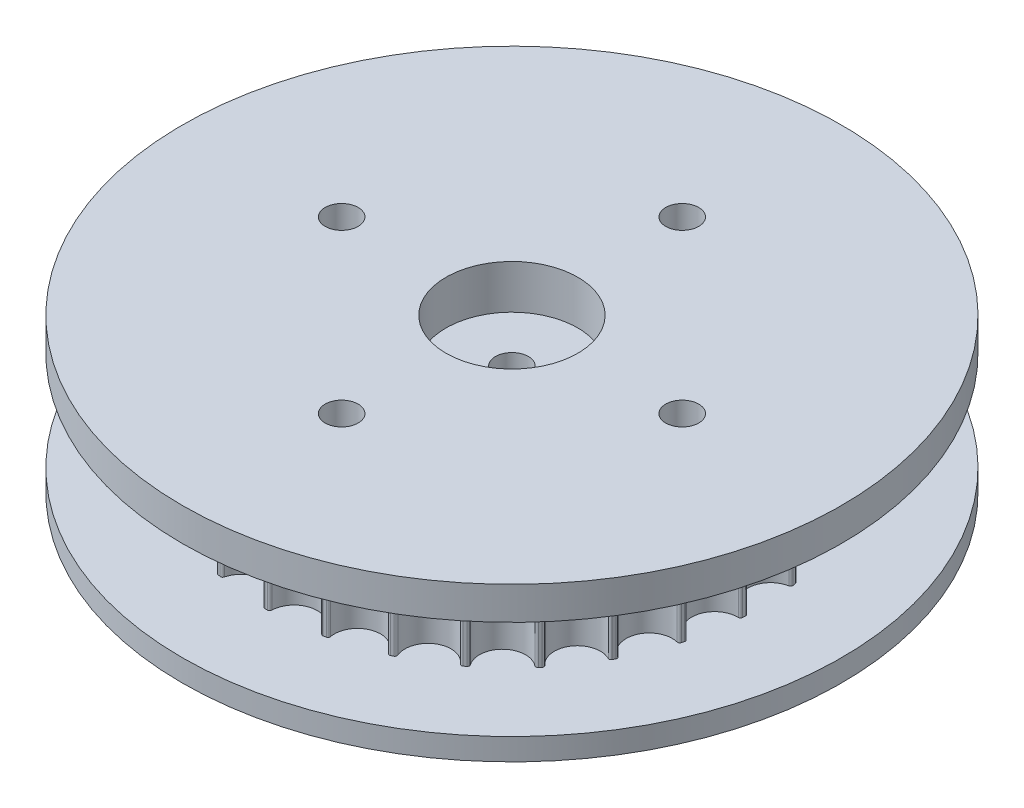
SolidWorks part; units mm, degrees
ref_plane "Front" through (0, 0, 0) normal (0, 0, 1) x (1, 0, 0)
ref_plane "Top" through (0, 0, 0) normal (0, 1, 0) x (1, 0, 0)
ref_plane "Right" through (0, 0, 0) normal (1, 0, 0) x (0, 0, -1)
sketch "Sketch1" plane through (0, 0, 0) normal (0, 1, 0) x (1, 0, 0)
  line L0 (0, 0) -> (0, 15.5) construction
  line L1 (0, 0) -> (15.5, 0) construction
  line L2 (0, 0) -> (0, -15.5) construction
  line L3 (0, 0) -> (-15.5, 0) construction
  circle A0 centre (0, 0) radius 30
  circle A1 centre (0, 0) radius 15.5 construction
  circle A2 centre (0, 15.5) radius 1.5
  circle A3 centre (15.5, 0) radius 1.5
  circle A4 centre (0, -15.5) radius 1.5
  circle A5 centre (-15.5, 0) radius 1.5
  circle A6 centre (0, 0) radius 1.5
  point P14 (0, 0)
  dimension "D1" = 60
  dimension "D2" = 31
  dimension "D3" = 3
  dimension "D5" = 3
  dimension "D4" = 4
extrude "Boss-Extrude1" add sketch "Sketch1" along normal blind 2
sketch "Sketch2" plane through (0, 2, 0) normal (0, 1, 0) x (1, 0, 0)
  line L0 (0, 0) -> (0, 15.5) construction
  line L1 (0, 0) -> (15.5, 0) construction
  line L2 (0, 0) -> (0, -15.5) construction
  line L3 (0, 0) -> (-15.5, 0) construction
  line L4 (0, 0) -> (0, 22.3727) construction
  line L5 (0, 0) -> (4.9707, 22.5821) construction
  line L6 (0, 0) -> (9.709, 20.9856) construction
  line L7 (0, 0) -> (13.9932, 18.4078) construction
  line L8 (0, 0) -> (17.6232, 14.9693) construction
  line L9 (0, 0) -> (20.4292, 10.8309) construction
  line L10 (0, 0) -> (22.2798, 6.186) construction
  line L11 (0, 0) -> (23.0888, 1.2518) construction
  line L12 (0, 0) -> (22.8181, -3.7408) construction
  line L13 (0, 0) -> (21.4804, -8.5586) construction
  line L14 (0, 0) -> (19.1384, -12.9761) construction
  line L15 (0, 0) -> (15.9014, -16.787) construction
  line L16 (0, 0) -> (11.921, -19.8128) construction
  line L17 (0, 0) -> (7.3831, -21.9123) construction
  line L18 (0, 0) -> (2.5, -22.9871) construction
  line L19 (0, 0) -> (-2.5, -22.9871) construction
  line L20 (0, 0) -> (-7.3831, -21.9123) construction
  line L21 (0, 0) -> (-11.921, -19.8128) construction
  line L22 (0, 0) -> (-15.9014, -16.787) construction
  line L23 (0, 0) -> (-19.1384, -12.9761) construction
  line L24 (0, 0) -> (-21.4804, -8.5586) construction
  line L25 (0, 0) -> (-22.0779, -3.6195) construction
  line L26 (0, 0) -> (-23.0888, 1.2518) construction
  line L27 (0, 0) -> (-22.2798, 6.186) construction
  line L28 (0, 0) -> (-20.4292, 10.8309) construction
  line L29 (0, 0) -> (-17.6232, 14.9693) construction
  line L30 (0, 0) -> (-13.9932, 18.4078) construction
  line L31 (0, 0) -> (-9.709, 20.9856) construction
  line L32 (0, 0) -> (-4.9707, 22.5821) construction
  line L33 (2.2986, 22.2543) -> (2.5392, 22.2281)
  line L34 (7.0288, 21.2399) -> (7.2582, 21.1626)
  line L35 (11.4304, 19.2323) -> (11.6379, 19.1075)
  line L36 (15.2976, 16.3255) -> (15.4733, 16.159)
  line L37 (18.4494, 12.6552) -> (18.5853, 12.4549)
  line L38 (20.7386, 8.3933) -> (20.8282, 8.1684)
  line L39 (22.058, 3.7389) -> (22.0972, 3.5)
  line L40 (22.3461, -1.0904) -> (22.333, -1.3321)
  line L41 (21.5892, -5.8686) -> (21.5245, -6.1019)
  line L42 (19.8229, -10.3725) -> (19.7095, -10.5863)
  line L43 (17.1297, -14.3913) -> (16.973, -14.5758)
  line L44 (13.6355, -17.7372) -> (13.4428, -17.8837)
  line L45 (9.5037, -20.2538) -> (9.2841, -20.3554)
  line L46 (4.9276, -21.8233) -> (4.6912, -21.8753)
  line L47 (0.121, -22.3723) -> (-0.121, -22.3723)
  line L48 (-4.6912, -21.8753) -> (-4.9276, -21.8233)
  line L49 (-9.2841, -20.3554) -> (-9.5037, -20.2538)
  line L50 (-13.4428, -17.8837) -> (-13.6355, -17.7372)
  line L51 (-16.973, -14.5758) -> (-17.1297, -14.3913)
  line L52 (-19.7095, -10.5863) -> (-19.8229, -10.3725)
  line L53 (-21.5245, -6.1019) -> (-21.5892, -5.8686)
  line L54 (-22.333, -1.3321) -> (-22.3461, -1.0904)
  line L55 (-22.0972, 3.5) -> (-22.058, 3.7389)
  line L56 (-20.8282, 8.1684) -> (-20.7386, 8.3933)
  line L57 (-18.5853, 12.4549) -> (-18.4494, 12.6552)
  line L58 (-15.4733, 16.159) -> (-15.2976, 16.3255)
  line L59 (-11.6379, 19.1075) -> (-11.4304, 19.2323)
  line L60 (-7.2582, 21.1626) -> (-7.0288, 21.2399)
  line L61 (-2.5392, 22.2281) -> (-2.2986, 22.2543)
  line L62 (0, 22.3727) -> (0, 23.8727) construction
  line L63 (4.8095, 21.8496) -> (4.9707, 22.5821) construction
  circle A0 centre (0, 15.5) radius 1.5
  circle A1 centre (0, 15.5) radius 1.5 construction
  circle A2 centre (15.5, 0) radius 1.5
  circle A3 centre (0, -15.5) radius 1.5
  circle A4 centre (-15.5, 0) radius 1.5
  circle A5 centre (0, 0) radius 20.2727 construction
  circle A6 centre (0, 0) radius 23.8727 construction
  circle A7 centre (0, 0) radius 22.3727 construction
  arc A8 (-2.0977, 22.2741) -> (2.0977, 22.2741) centre (0, 22.3727) ccw construction
  arc A9 (-2.2986, 22.2543) -> (-2.0799, 22.0829) centre (-2.278, 22.0553) cw
  arc A10 (2.2986, 22.2543) -> (2.0799, 22.0829) centre (2.278, 22.0553) ccw
  arc A11 (-2.0799, 22.0829) -> (2.0799, 22.0829) centre (0, 22.3727) ccw
  arc A12 (2.5392, 22.2281) -> (2.7159, 22.0138) centre (2.5165, 22.0294) cw
  arc A13 (2.7159, 22.0138) -> (6.7785, 21.1195) centre (4.8095, 21.8496) ccw
  arc A14 (7.0288, 21.2399) -> (6.7785, 21.1195) centre (6.966, 21.05) ccw
  arc A15 (7.2582, 21.1626) -> (7.3847, 20.9153) centre (7.1933, 20.9734) cw
  arc A16 (7.3847, 20.9153) -> (11.1601, 19.1686) centre (9.394, 20.3049) ccw
  arc A17 (11.4304, 19.2323) -> (11.1601, 19.1686) centre (11.3283, 19.0604) ccw
  arc A18 (11.6379, 19.1075) -> (11.7082, 18.8388) centre (11.5338, 18.9367) cw
  arc A19 (11.7082, 18.8388) -> (15.0198, 16.3214) centre (13.5394, 17.8107) ccw
  arc A20 (15.2976, 16.3255) -> (15.0198, 16.3214) centre (15.1608, 16.1795) ccw
  arc A21 (15.4733, 16.159) -> (15.4843, 15.8814) centre (15.335, 16.0145) cw
  arc A22 (15.4843, 15.8814) -> (18.1773, 12.711) centre (17.0516, 14.4838) ccw
  arc A23 (18.4494, 12.6552) -> (18.1773, 12.711) centre (18.2845, 12.5421) ccw
  arc A24 (18.5853, 12.4549) -> (18.5363, 12.1815) centre (18.4191, 12.3435) cw
  arc A25 (18.5363, 12.1815) -> (20.4848, 8.5062) centre (19.7665, 10.4795) ccw
  arc A26 (20.7386, 8.3933) -> (20.4848, 8.5062) centre (20.5532, 8.3183) ccw
  arc A27 (20.8282, 8.1684) -> (20.7216, 7.9119) centre (20.642, 8.0954) cw
  arc A28 (20.7216, 7.9119) -> (21.8344, 3.9037) centre (21.5572, 5.9853) ccw
  arc A29 (22.058, 3.7389) -> (21.8344, 3.9037) centre (21.8608, 3.7055) ccw
  arc A30 (22.0972, 3.5) -> (21.9379, 3.2724) centre (21.8997, 3.4687) cw
  arc A31 (21.9379, 3.2724) -> (22.1631, -0.8813) centre (22.3399, 1.2112) ccw
  arc A32 (22.3461, -1.0904) -> (22.1631, -0.8813) centre (22.1463, -1.0806) ccw
  arc A33 (22.333, -1.3321) -> (22.1285, -1.5201) centre (22.1333, -1.3202) cw
  arc A34 (22.1285, -1.5201) -> (21.4555, -5.6251) centre (22.0779, -3.6195) ccw
  arc A35 (21.5892, -5.8686) -> (21.4555, -5.6251) centre (21.3963, -5.8162) ccw
  arc A36 (21.5245, -6.1019) -> (21.2844, -6.2415) centre (21.3321, -6.0473) cw
  arc A37 (21.2844, -6.2415) -> (19.7447, -10.1059) centre (20.7837, -8.281) ccw
  arc A38 (19.8229, -10.3725) -> (19.7447, -10.1059) centre (19.6457, -10.2797) ccw
  arc A39 (19.7095, -10.5863) -> (19.445, -10.6711) centre (19.5333, -10.4917) cw
  arc A40 (19.445, -10.6711) -> (17.1106, -14.1142) centre (18.5176, -12.5553) ccw
  arc A41 (17.1297, -14.3913) -> (17.1106, -14.1142) centre (16.9766, -14.2626) ccw
  arc A42 (16.973, -14.5758) -> (16.6964, -14.6017) centre (16.8213, -14.4455) cw
  arc A43 (16.6964, -14.6017) -> (13.6764, -17.4625) centre (15.3857, -16.2425) ccw
  arc A44 (13.6355, -17.7372) -> (13.6764, -17.4625) centre (13.5136, -17.5787) ccw
  arc A45 (13.4428, -17.8837) -> (13.1671, -17.8496) centre (13.3226, -17.7238) cw
  arc A46 (13.1671, -17.8496) -> (9.6027, -19.9942) centre (11.5343, -19.1702) ccw
  arc A47 (9.5037, -20.2538) -> (9.6027, -19.9942) centre (9.4188, -20.0727) ccw
  arc A48 (9.2841, -20.3554) -> (9.0222, -20.2628) centre (9.2011, -20.1734) cw
  arc A49 (9.0222, -20.2628) -> (5.0801, -21.5911) centre (7.1436, -21.2015) ccw
  arc A50 (4.9276, -21.8233) -> (5.0801, -21.5911) centre (4.8835, -21.6282) ccw
  arc A51 (4.6912, -21.8753) -> (4.4553, -21.7286) centre (4.6493, -21.6798) cw
  arc A52 (4.4553, -21.7286) -> (0.3199, -22.1784) centre (2.4189, -22.2415) ccw
  arc A53 (0.121, -22.3723) -> (0.3199, -22.1784) centre (0.12, -22.1723) ccw
  arc A54 (-0.121, -22.3723) -> (-0.3199, -22.1784) centre (-0.12, -22.1723) cw
  arc A55 (-0.3199, -22.1784) -> (-4.4553, -21.7286) centre (-2.4189, -22.2415) ccw
  arc A56 (-4.6912, -21.8753) -> (-4.4553, -21.7286) centre (-4.6493, -21.6798) ccw
  arc A57 (-4.9276, -21.8233) -> (-5.0801, -21.5911) centre (-4.8835, -21.6282) cw
  arc A58 (-5.0801, -21.5911) -> (-9.0222, -20.2628) centre (-7.1436, -21.2015) ccw
  arc A59 (-9.2841, -20.3554) -> (-9.0222, -20.2628) centre (-9.2011, -20.1734) ccw
  arc A60 (-9.5037, -20.2538) -> (-9.6027, -19.9942) centre (-9.4188, -20.0727) cw
  arc A61 (-9.6027, -19.9942) -> (-13.1671, -17.8496) centre (-11.5343, -19.1702) ccw
  arc A62 (-13.4428, -17.8837) -> (-13.1671, -17.8496) centre (-13.3226, -17.7238) ccw
  arc A63 (-13.6355, -17.7372) -> (-13.6764, -17.4625) centre (-13.5136, -17.5787) cw
  arc A64 (-13.6764, -17.4625) -> (-16.6964, -14.6017) centre (-15.3857, -16.2425) ccw
  arc A65 (-16.973, -14.5758) -> (-16.6964, -14.6017) centre (-16.8213, -14.4455) ccw
  arc A66 (-17.1297, -14.3913) -> (-17.1106, -14.1142) centre (-16.9766, -14.2626) cw
  arc A67 (-17.1106, -14.1142) -> (-19.445, -10.6711) centre (-18.5176, -12.5553) ccw
  arc A68 (-19.7095, -10.5863) -> (-19.445, -10.6711) centre (-19.5333, -10.4917) ccw
  arc A69 (-19.8229, -10.3725) -> (-19.7447, -10.1059) centre (-19.6457, -10.2797) cw
  arc A70 (-19.7447, -10.1059) -> (-21.2844, -6.2415) centre (-20.7837, -8.281) ccw
  arc A71 (-21.5245, -6.1019) -> (-21.2844, -6.2415) centre (-21.3321, -6.0473) ccw
  arc A72 (-21.5892, -5.8686) -> (-21.4555, -5.6251) centre (-21.3963, -5.8162) cw
  arc A73 (-21.4555, -5.6251) -> (-22.1285, -1.5201) centre (-22.0779, -3.6195) ccw
  arc A74 (-22.333, -1.3321) -> (-22.1285, -1.5201) centre (-22.1333, -1.3202) ccw
  arc A75 (-22.3461, -1.0904) -> (-22.1631, -0.8813) centre (-22.1463, -1.0806) cw
  arc A76 (-22.1631, -0.8813) -> (-21.9379, 3.2724) centre (-22.3399, 1.2112) ccw
  arc A77 (-22.0972, 3.5) -> (-21.9379, 3.2724) centre (-21.8997, 3.4687) ccw
  arc A78 (-22.058, 3.7389) -> (-21.8344, 3.9037) centre (-21.8608, 3.7055) cw
  arc A79 (-21.8344, 3.9037) -> (-20.7216, 7.9119) centre (-21.5572, 5.9853) ccw
  arc A80 (-20.8282, 8.1684) -> (-20.7216, 7.9119) centre (-20.642, 8.0954) ccw
  arc A81 (-20.7386, 8.3933) -> (-20.4848, 8.5062) centre (-20.5532, 8.3183) cw
  arc A82 (-20.4848, 8.5062) -> (-18.5363, 12.1815) centre (-19.7665, 10.4795) ccw
  arc A83 (-18.5853, 12.4549) -> (-18.5363, 12.1815) centre (-18.4191, 12.3435) ccw
  arc A84 (-18.4494, 12.6552) -> (-18.1773, 12.711) centre (-18.2845, 12.5421) cw
  arc A85 (-18.1773, 12.711) -> (-15.4843, 15.8814) centre (-17.0516, 14.4838) ccw
  arc A86 (-15.4733, 16.159) -> (-15.4843, 15.8814) centre (-15.335, 16.0145) ccw
  arc A87 (-15.2976, 16.3255) -> (-15.0198, 16.3214) centre (-15.1608, 16.1795) cw
  arc A88 (-15.0198, 16.3214) -> (-11.7082, 18.8388) centre (-13.5394, 17.8107) ccw
  arc A89 (-11.6379, 19.1075) -> (-11.7082, 18.8388) centre (-11.5338, 18.9367) ccw
  arc A90 (-11.4304, 19.2323) -> (-11.1601, 19.1686) centre (-11.3283, 19.0604) cw
  arc A91 (-11.1601, 19.1686) -> (-7.3847, 20.9153) centre (-9.394, 20.3049) ccw
  arc A92 (-7.2582, 21.1626) -> (-7.3847, 20.9153) centre (-7.1933, 20.9734) ccw
  arc A93 (-7.0288, 21.2399) -> (-6.7785, 21.1195) centre (-6.966, 21.05) cw
  arc A94 (-6.7785, 21.1195) -> (-2.7159, 22.0138) centre (-4.8095, 21.8496) ccw
  arc A95 (-2.5392, 22.2281) -> (-2.7159, 22.0138) centre (-2.5165, 22.0294) ccw
  circle A96 centre (0, 0) radius 23.1227 construction
  point P16 (0, 0)
  point P19 (0, 23.1227)
  point P29 (2.3743, 22.2463)
  point P255 (0, 0)
  point P256 (-21.9884, -4.1289)
  point P312 (0, 0)
  dimension "D2" = 2.1
  dimension "D3" = 3.6
  dimension "D4" = 0.2
  dimension "D6" = 5
  dimension "D1" = 4
  dimension "D5" = 29
  dimension "D7" = 29
extrude "Boss-Extrude2" add sketch "Sketch2" along normal blind 9
sketch "Sketch3" plane through (0, 11, 0) normal (0, 1, 0) x (1, 0, 0)
  line L0 (0, 15.5) -> (0, 0) construction
  line L1 (15.5, 0) -> (0, 0) construction
  line L2 (0, -15.5) -> (0, 0) construction
  line L3 (-15.5, 0) -> (0, 0) construction
  circle A0 centre (0, 15.5) radius 1.5
  circle A1 centre (0, 15.5) radius 1.5 construction
  circle A2 centre (15.5, 0) radius 1.5
  circle A3 centre (0, -15.5) radius 1.5
  circle A4 centre (-15.5, 0) radius 1.5
  circle A5 centre (0, 0) radius 30
  circle A6 centre (0, 0) radius 30 construction
  point P15 (0, 0)
  dimension "D1" = 4
extrude "Boss-Extrude3" add sketch "Sketch3" along normal blind 3
sketch "Sketch4" plane through (0, 14, 0) normal (0, 1, 0) x (1, 0, 0)
  circle A0 centre (0, 0) radius 6
  dimension "D1" = 12
extrude "Cut-Extrude1" cut sketch "Sketch4" against normal blind 4
sketch "Sketch5" plane through (0, 2, 0) normal (0, -1, 0) x (1, 0, 0)
  circle A0 centre (0, 0) radius 1.5
  circle A1 centre (0, 0) radius 1.5 construction
extrude "Cut-Extrude2" cut sketch "Sketch5" against normal through all
